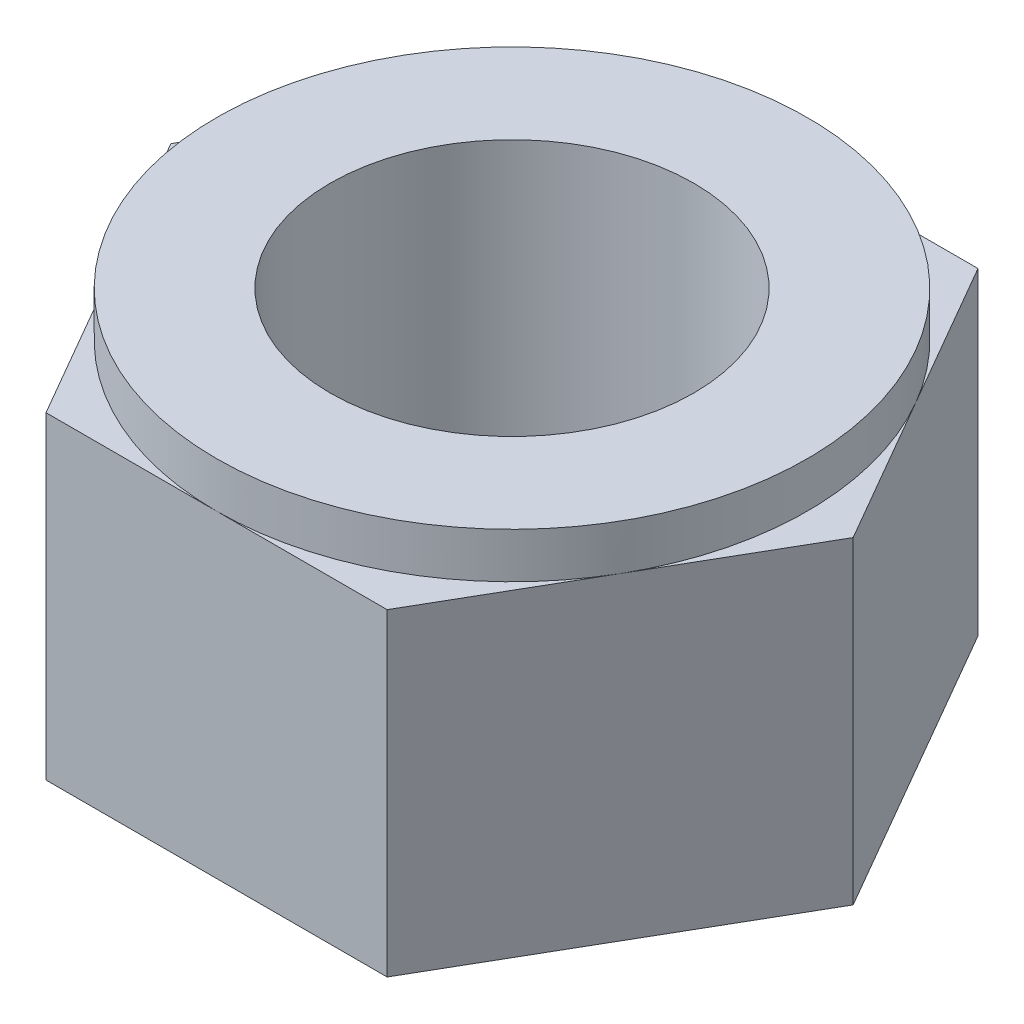
SolidWorks part; units mm, degrees
ref_plane "前视基准面" through (0, 0, 0) normal (0, 0, 1) x (1, 0, 0)
ref_plane "上视基准面" through (0, 0, 0) normal (0, 1, 0) x (1, 0, 0)
ref_plane "右视基准面" through (0, 0, 0) normal (1, 0, 0) x (0, 0, -1)
other "Configuration Table"
sketch "草图1" plane through (0, 0, 0) normal (0, 1, 0) x (1, 0, 0)
  line L1 (7.5056, 0) -> (3.7528, 6.5)
  line L2 (3.7528, 6.5) -> (-3.7528, 6.5)
  line L3 (-3.7528, 6.5) -> (-7.5056, 0)
  line L4 (-7.5056, 0) -> (-3.7528, -6.5)
  line L5 (-3.7528, -6.5) -> (3.7528, -6.5)
  line L6 (3.7528, -6.5) -> (7.5056, 0)
  circle A0 centre (0, 0) radius 6.5 construction
  dimension "D1" = 13
extrude "凸台-拉伸1" add sketch "草图1" along normal blind 7
sketch "草图2" plane through (0, 7, 0) normal (0, 1, 0) x (1, 0, 0)
  line L0 (3.7528, -6.5) -> (7.5056, 0) construction
  circle A0 centre (0, 0) radius 6.5
extrude "凸台-拉伸2" add sketch "草图2" along normal blind 1
sketch "草图3" plane through (0, 0, 0) normal (0, -1, 0) x (1, 0, 0)
  circle A0 centre (0, 0) radius 4
  dimension "D1" = 8
extrude "切除-拉伸1" cut sketch "草图3" against normal through all
ref_axis "基准轴1" through (0, 11.2881, 0) along (0, -1, 0)
